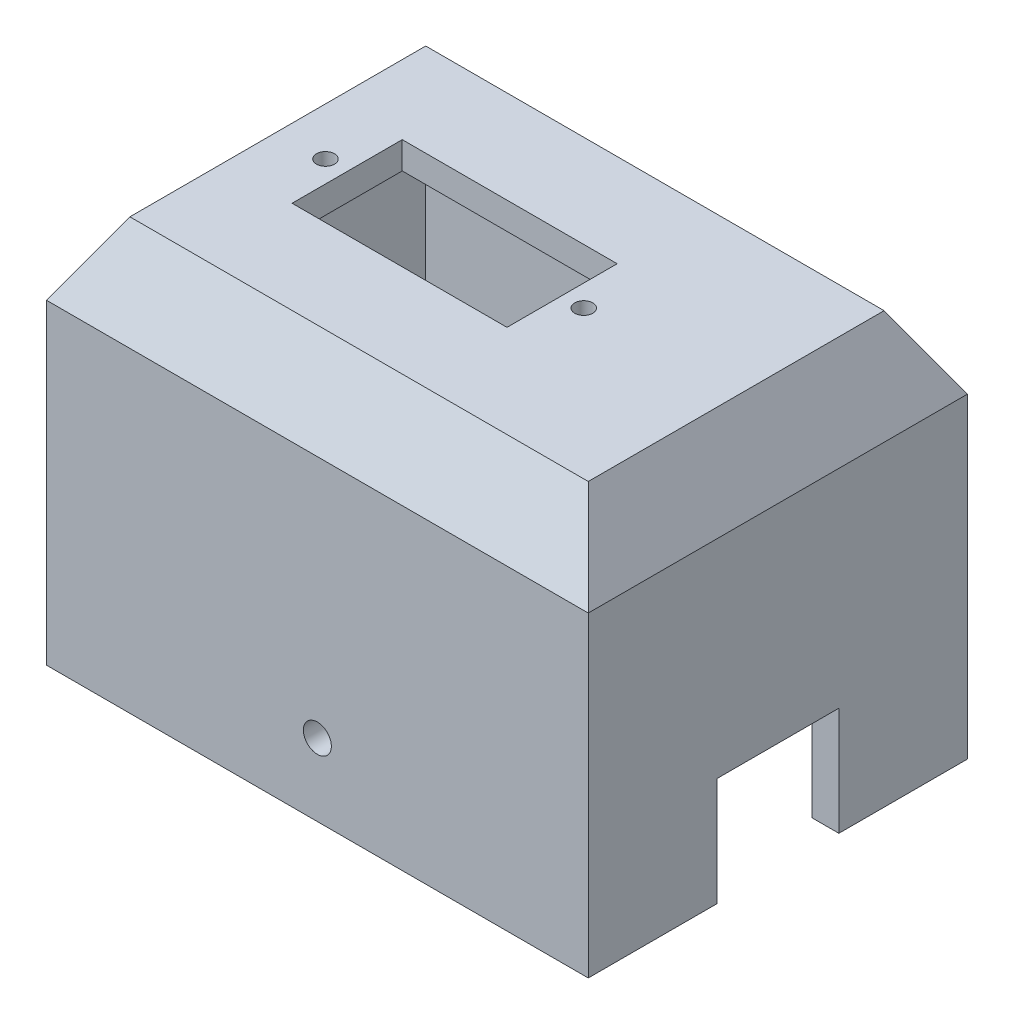
SolidWorks part; units mm, degrees
ref_plane "前视基准面" through (0, 0, 0) normal (0, 0, 1) x (1, 0, 0)
ref_plane "上视基准面" through (0, 0, 0) normal (0, 1, 0) x (1, 0, 0)
ref_plane "右视基准面" through (0, 0, 0) normal (1, 0, 0) x (0, 0, -1)
sketch "草图47" plane through (0, 0, 0) normal (0, 1, 0) x (1, 0, 0)
  line L1 (30, -21) -> (-30, -21)
  line L2 (30, -21) -> (30, 21)
  line L3 (30, 21) -> (-30, 21)
  line L4 (-30, -21) -> (-30, 21)
  line L5 (30, -21) -> (-30, 21) construction
  line L6 (30, 21) -> (-30, -21) construction
  point P0 (0, 0)
  dimension "D1" = 42
  dimension "D2" = 60
extrude "凸台-拉伸4" add sketch "草图47" along normal blind 43
chamfer "倒角1" distance 8 angle 30 4 edges at (0, 43, -21) (30, 43, 0) (0, 43, 21) (-30, 43, 0) first distance on face at (0, 21.5, -21) first distance on face at (30, 21.5, 0) first distance on face at (0, 21.5, 21) first distance on face at (-30, 21.5, 0)
shell "抽壳1" thickness 3 removed face at (0, 0, 0)
sketch "草图48" plane through (0, 43, -43) normal (0, -1, 0) x (1, 0, 0)
  line L0 (-5.8, 47.679) -> (-5.8, 60.2141) construction
  line L1 (6.1, 36.9) -> (-17.7, 36.9)
  line L2 (6.1, 36.9) -> (6.1, 49.1)
  line L3 (6.1, 49.1) -> (-17.7, 49.1)
  line L4 (-17.7, 36.9) -> (-17.7, 49.1)
  line L5 (6.1, 36.9) -> (-17.7, 49.1) construction
  line L6 (6.1, 49.1) -> (-17.7, 36.9) construction
  line L13 (-20.1, 43) -> (-5.8, 43) construction
  circle A0 centre (-20.1, 43) radius 1
  circle A2 centre (8.5, 43) radius 1
  circle A3 centre (0, 43) radius 6.1 construction
  point P0 (-5.8, 43)
  point P6 (-5.8, 43)
  point P7 (0, 0)
  point P10 (0, 43)
  dimension "D4" = 2
  dimension "D1" = 23.8
  dimension "D2" = 12.2
  dimension "D3" = 14.3
extrude "切除-拉伸3" cut sketch "草图48" along normal up to next
sketch "草图49" plane through (0, 0, -21) normal (0, 0, -1) x (-1, 0, 0)
  line L0 (-30, 0) -> (30, 0) construction
  circle A0 centre (0, 8) radius 1.55
  point P4 (0, 0)
  point P5 (0, 0)
  dimension "D1" = 3.1
  dimension "D2" = 8
extrude "切除-拉伸4" cut sketch "草图49" against normal through all
sketch "草图50" plane through (30, 0, 0) normal (1, 0, 0) x (0, 0, -1)
  line L0 (-21, 0) -> (21, 0) construction
  line L1 (6.75, 12) -> (-6.75, 12)
  line L2 (6.75, 12) -> (6.75, 0)
  line L3 (6.75, 0) -> (-6.75, 0)
  line L4 (-6.75, 12) -> (-6.75, 0)
  line L5 (6.75, 12) -> (-6.75, 0) construction
  line L6 (6.75, 0) -> (-6.75, 12) construction
  point P0 (0, 6)
  dimension "D1" = 12
  dimension "D2" = 13.5
extrude "切除-拉伸5" cut sketch "草图50" against normal up to next
sketch "草图51" plane through (-30, 0, 0) normal (-1, 0, 0) x (0, 0, 1)
  line L0 (-21, 0) -> (21, 0) construction
  line L1 (4.4906, 13.7619) -> (-4.4906, 13.7619)
  line L2 (4.4906, 13.7619) -> (4.4906, 0)
  line L3 (4.4906, 0) -> (-4.4906, 0)
  line L4 (-4.4906, 13.7619) -> (-4.4906, 0)
  line L5 (4.4906, 13.7619) -> (-4.4906, 0) construction
  line L6 (4.4906, 0) -> (-4.4906, 13.7619) construction
  point P0 (0, 6.881)
extrude "切除-拉伸6" cut sketch "草图51" against normal up to next
